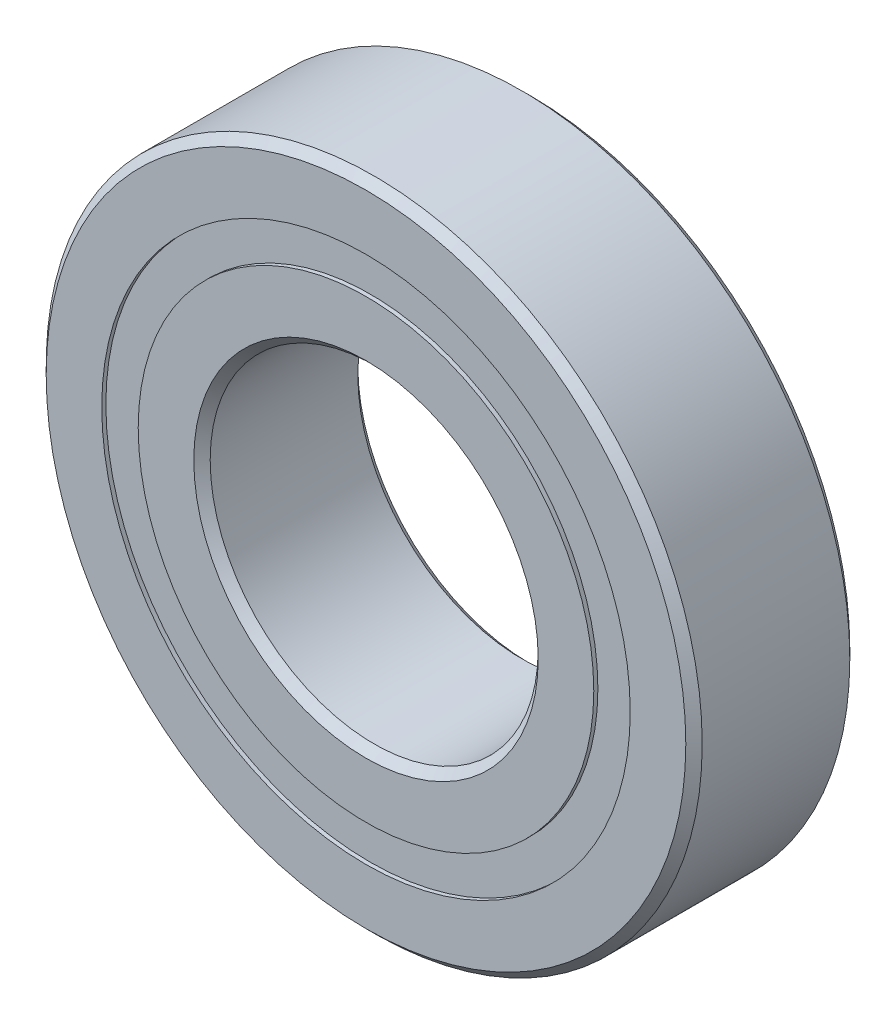
SolidWorks part; units mm, degrees
ref_plane "Front Plane" through (0, 0, 0) normal (0, 0, 1) x (1, 0, 0)
ref_plane "Top Plane" through (0, 0, 0) normal (0, 1, 0) x (1, 0, 0)
ref_plane "Right Plane" through (0, 0, 0) normal (1, 0, 0) x (0, 0, -1)
sketch "Sketch1" plane through (0, 0, 0) normal (1, 0, 0) x (0, 0, -1)
  line L0 (-2, 0) -> (2, 0) construction
  line L1 (0, 8) -> (0, -8) construction
  line L2 (1.8, 8) -> (-1.8, 8)
  line L3 (-1.8, 8) -> (-2, 7.8)
  line L4 (-2, 7.8) -> (-2, 6.4444)
  line L5 (-2, 6.4444) -> (-0.8889, 6.4444)
  line L6 (2, 6.4444) -> (0.8889, 6.4444)
  line L7 (2, 7.8) -> (2, 6.4444)
  line L8 (1.8, 8) -> (2, 7.8)
  line L9 (0, 8) -> (0, 6) construction
  line L10 (0, 6) -> (0, 4) construction
  arc A0 (-0.8889, 6.4444) -> (0.8889, 6.4444) centre (0, 6) cw
  arc A1 (-0.8889, 6.4444) -> (0.8889, 6.4444) centre (0, 6) ccw construction
  point P14 (0, 4)
  point P15 (0, -4)
  dimension "Width" = 4
  dimension "OD" = 16
  dimension "D1" = 45
  dimension "D2" = 0.2
  dimension "D3" = 1.7778
  dimension "Shaft Dia" = 8
  dimension "D4" = 0.4444
revolve "Revolve1" add sketch "Sketch1" angle 360 about L0
sketch "Sketch2" plane through (0, 0, 0) normal (1, 0, 0) x (0, 0, -1)
  line L0 (-2, 5.5556) -> (-0.8889, 5.5556)
  line L1 (-2, 7.8) -> (-2, -7.8) construction
  line L2 (-2, 5.5556) -> (-2, 4.2)
  line L3 (-2, 4.2) -> (-1.8, 4)
  line L4 (-1.8, 4) -> (1.8, 4)
  line L5 (0, 8) -> (0, -8) construction
  line L6 (0, 4) -> (0, 5.0062) construction
  line L7 (0, 5.0062) -> (0, 4) construction
  line L8 (-2, 5.5556) -> (-2, 2.8444) construction
  line L10 (2, 5.5556) -> (0.8889, 5.5556)
  line L11 (2, 5.5556) -> (2, 4.2)
  line L12 (2, 4.2) -> (1.8, 4)
  arc A0 (-0.8889, 5.5556) -> (0.8889, 5.5556) centre (0, 6) ccw
  arc A1 (0.8889, 6.4444) -> (-0.8889, 6.4444) centre (0, 6) ccw construction
  circle A2 centre (0, 6) radius 0.9938 construction
  dimension "D1" = 0.2
  dimension "D2" = 45
revolve "Revolve2" add sketch "Sketch2" angle 360 about L0
sketch "Sketch3" plane through (0, 0, 0) normal (1, 0, 0) x (0, 0, -1)
  line L0 (-0.9938, 6) -> (0.9938, 6)
  line L1 (0, 6) -> (0, 0) construction
  circle A1 centre (0, 6) radius 0.9938 construction
  arc A2 (-0.9938, 6) -> (0.9938, 6) centre (0, 6) cw
  arc A3 (0.8889, 6.4444) -> (-0.8889, 6.4444) centre (0, 6) ccw construction
  dimension "D1" = 1.9876
  dimension "D2" = 6
revolve "Revolve3" add sketch "Sketch3" angle 360 about L0
ref_axis "Axis1" through (0, 0, -2) along (0, 0, 1)
pattern_circular "CirPattern1" count 18 every 20 about axis through (0, 0, -2) along (0, 0, 1) of bodies 104
sketch "Sketch5" plane through (0, 0, 0) normal (1, 0, 0) x (0, 0, -1)
  line L0 (-2, 5.5556) -> (-0.8889, 5.5556) construction
  line L1 (-1.9, 6.4444) -> (-0.9938, 6.4444)
  line L2 (-1.9, 6.4444) -> (-1.9, 5.5556)
  line L3 (-1.9, 5.5556) -> (-0.9938, 5.5556)
  line L4 (-0.9938, 6.4444) -> (-0.9938, 5.5556)
  line L5 (0.9938, 6.4444) -> (1.9, 6.4444)
  line L6 (0.9938, 6.4444) -> (0.9938, 5.5556)
  line L7 (0.9938, 5.5556) -> (1.9, 5.5556)
  line L8 (1.9, 6.4444) -> (1.9, 5.5556)
  line L9 (-2, 6.4444) -> (-0.8889, 6.4444) construction
  line L10 (-1.9, 7.9) -> (-1.9, 6.4444) construction
  line L11 (-1.8, 8) -> (-2, 7.8) construction
  circle A0 centre (0, 6) radius 0.9938 construction
revolve "Revolve5" add sketch "Sketch5" angle 360 about L0
sketch "Sketch6" plane through (0, 0, 0) normal (0, 1, 0) x (1, 0, 0)
  point P0 (8, -2)
  point P1 (8, 2)
ref_axis "Center Axis 1" through (0, 0, -3.9722) along (0, 0, 1)
ref_plane "Contact Plane 1" through (0, 0, 2) normal (0, 0, 1) x (1, 0, 0)
ref_plane "Contact Plane 2" through (0, 0, -2) normal (0, 0, -1) x (-1, 0, 0)
equation "\"D2@Sketch1\" = \"Width@Sketch1\"*.05"
equation "\"D3@Sketch1\" = \"Width@Sketch1\"/2.25"
equation "\"D4@Sketch1\" = \"D3@Sketch1\"/4"
equation "\"Balls@CirPattern1\"=\"D2@Sketch3\"*2*pi/\"D1@Sketch3\"-1"
equation "\"D2@CirPattern1\" = 360/\"Balls@CirPattern1\""
equation "\"D1@Sketch2\"=\"D2@Sketch1\""
equation "\"D1@Sketch6\"=\"Width@Sketch1\""
